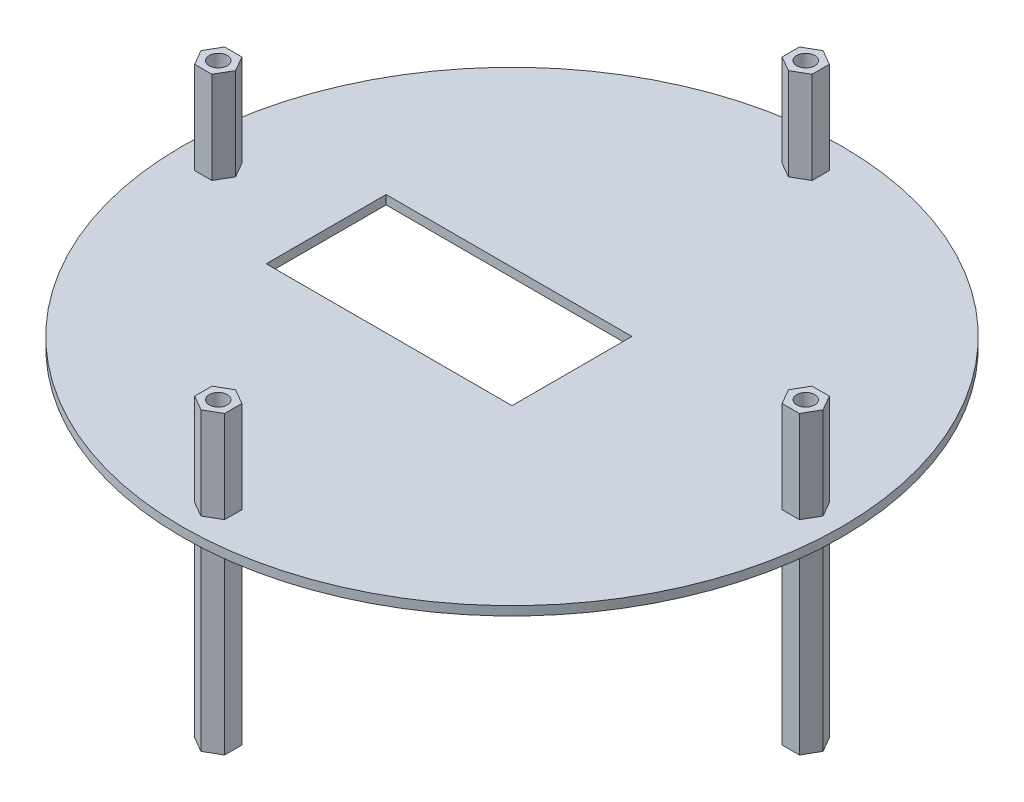
SolidWorks part; units mm, degrees
ref_plane "前视基准面" through (0, 0, 0) normal (0, 0, 1) x (1, 0, 0)
ref_plane "上视基准面" through (0, 0, 0) normal (0, 1, 0) x (1, 0, 0)
ref_plane "右视基准面" through (0, 0, 0) normal (1, 0, 0) x (0, 0, -1)
sketch "草图1" plane through (0, 0, 0) normal (0, 1, 0) x (1, 0, 0)
  circle A0 centre (0, 0) radius 55
  dimension "D1" = 110
extrude "凸台-拉伸1" add sketch "草图1" along normal blind 1.5 contours A0
sketch "草图2" plane through (0, 1.5, 0) normal (0, 1, 0) x (1, 0, 0)
  line L0 (-55, 0) -> (55, 0) construction
  line L1 (0, 55) -> (0, -55) construction
  line L2 (10, 10) -> (-31, 10)
  line L3 (0, 0) -> (10, 0) construction
  line L4 (0, 0) -> (0, 10) construction
  line L15 (-31, 10) -> (-31, -10)
  line L16 (-31, -10) -> (10, -10)
  line L17 (10, -10) -> (10, 10)
  circle A0 centre (0, 0) radius 55 construction
  dimension "D1" = 10
  dimension "D2" = 10
  dimension "D3" = 41
  dimension "D4" = 20
extrude "切除-拉伸1" cut sketch "草图2" against normal blind 1.5
sketch "草图3" plane through (0, 1.5, 0) normal (0, 1, 0) x (1, 0, 0)
  line L0 (-55, 0) -> (55, 0) construction
  line L1 (0, 55) -> (0, -55) construction
  line L2 (-2.5, 47.5566) -> (0, 46.1132)
  line L3 (-46.1132, 0) -> (-47.5566, 2.5)
  line L4 (-47.5566, 2.5) -> (-50.4434, 2.5)
  line L5 (-50.4434, 2.5) -> (-51.8868, 0)
  line L6 (-51.8868, 0) -> (-50.4434, -2.5)
  line L7 (-50.4434, -2.5) -> (-47.5566, -2.5)
  line L8 (-47.5566, -2.5) -> (-46.1132, 0)
  line L9 (-2.5, 50.4434) -> (-2.5, 47.5566)
  line L10 (0, 51.8868) -> (-2.5, 50.4434)
  line L11 (2.5, 50.4434) -> (0, 51.8868)
  line L12 (2.5, 47.5566) -> (2.5, 50.4434)
  line L13 (0, 46.1132) -> (2.5, 47.5566)
  line L14 (47.5566, 2.5) -> (46.1132, 0)
  line L15 (50.4434, 2.5) -> (47.5566, 2.5)
  line L16 (51.8868, 0) -> (50.4434, 2.5)
  line L17 (50.4434, -2.5) -> (51.8868, 0)
  line L18 (47.5566, -2.5) -> (50.4434, -2.5)
  line L19 (46.1132, 0) -> (47.5566, -2.5)
  line L20 (2.5, -47.5566) -> (0, -46.1132)
  line L21 (2.5, -50.4434) -> (2.5, -47.5566)
  line L22 (0, -51.8868) -> (2.5, -50.4434)
  line L23 (-2.5, -50.4434) -> (0, -51.8868)
  line L24 (-2.5, -47.5566) -> (-2.5, -50.4434)
  line L25 (0, -46.1132) -> (-2.5, -47.5566)
  circle A0 centre (0, 0) radius 55 construction
  circle A1 centre (-49, 0) radius 2.5 construction
  circle A2 centre (-49, 0) radius 1.5
  circle A3 centre (0, 49) radius 1.5
  circle A4 centre (49, 0) radius 1.5
  circle A5 centre (0, -49) radius 1.5
  point P7 (-49, 0)
  point P37 (0, 0)
  point P45 (0, 0)
  dimension "D4" = 3
  dimension "D1" = 6
  dimension "D2" = 5
  dimension "D3" = 4
  dimension "D5" = 4
extrude "凸台-拉伸3" add sketch "草图3" against normal blind 34
sketch "草图5" plane through (0, 1.5, 0) normal (0, 1, 0) x (1, 0, 0)
  circle A0 centre (0, 0) radius 3.391
extrude "凸台-拉伸4" add sketch "草图3<3>" along normal blind 15.35
sketch "草图3<3>" plane through (0, 1.5, 0) normal (0, 1, 0) x (1, 0, 0) same geometry as "草图3"
